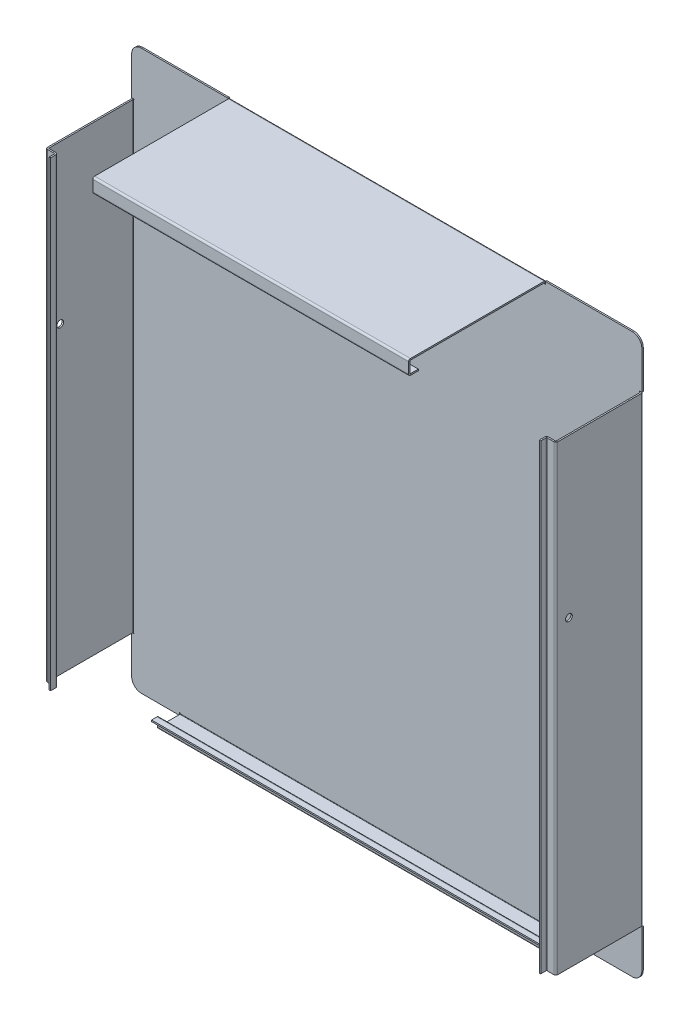
SolidWorks part; units mm, degrees
note: The reader was unsure of these and kept them because the rebuilt part matched: flange length of "边线-法兰1", "边线-法兰4", "边线-法兰5", "边线-法兰2", "边线-法兰3", "边线-法兰6", "边线-法兰7".
ref_plane "前视基准面" through (0, 0, 0) normal (0, 0, 1) x (1, 0, 0)
ref_plane "上视基准面" through (0, 0, 0) normal (0, 1, 0) x (1, 0, 0)
ref_plane "右视基准面" through (0, 0, 0) normal (1, 0, 0) x (0, 0, -1)
sketch "草图2" plane through (0, 0, 0) normal (0, 0, 1) x (1, 0, 0)
  line L1 (-525, 575) -> (525, 575)
  line L2 (-525, 575) -> (-525, -575)
  line L3 (-525, -575) -> (525, -575)
  line L4 (525, 575) -> (525, -575)
  line L5 (-525, 575) -> (525, -575) construction
  line L6 (-525, -575) -> (525, 575) construction
  point P0 (0, 0)
  dimension "D1" = 1050
  dimension "D2" = 1150
base flange "基体-法兰1" sketch "草图2" thickness 3 reverse thickness direction no parameters "D1"=0.7366
edge flange "边线-法兰1" sketch "草图12" flange profiles "草图12", "草图13" flange angle 90 flange length 180 flange position material inside bend radius 0.7366 thickness 3 relief rectangular parameters "D6"=10, "D8"=1
sketch "草图12" plane through (-525, 0, 0) normal (-1, 0, 0) x (0, -1, 0)
  line L0 (-575, 0) -> (575, 0) construction
  line L1 (-475, 0) -> (475, 0)
  line L2 (-475, 0) -> (-475, 177)
  line L3 (-475, 177) -> (475, 177)
  line L4 (475, 177) -> (475, 0)
  dimension "D1" = 100
  dimension "D2" = 100
sketch "草图13" plane through (525, 0, 0) normal (1, 0, 0) x (0, 1, 0)
  line L0 (-575, 0) -> (575, 0) construction
  line L1 (-475, 0) -> (475, 0)
  line L2 (-475, 0) -> (-475, 177)
  line L3 (-475, 177) -> (475, 177)
  line L4 (475, 177) -> (475, 0)
bend "边线折弯2" bend radius 0.7366 bend angle 90 parameters "D5"=2
bend "边线折弯3" bend radius 0.7366 bend angle 90 parameters "D5"=3
edge flange "边线-法兰4" sketch "草图42" flange angle 90 flange length 50 flange position material inside bend radius 0.7366 thickness 3 relief rectangular parameters "D6"=10
sketch "草图42" plane through (0, -575, 0) normal (0, -1, 0) x (1, 0, 0)
  line L0 (-525, 0) -> (525, 0) construction
  line L1 (-425, 0) -> (425, 0)
  line L2 (-425, 0) -> (-425, 47)
  line L3 (-425, 47) -> (425, 47)
  line L4 (425, 47) -> (425, 0)
  line L5 (-525, 0.7366) -> (-525, 177) construction
  line L8 (-525, -3) -> (525, -3) construction
  dimension "D1" = 850
  dimension "D2" = 50
  dimension "D3" = 100
bend "边线折弯13" bend radius 0.7366 bend angle 90 parameters "D5"=5
edge flange "边线-法兰5" sketch "草图49" flange angle 90 flange length 283 flange position material inside bend radius 0.7366 thickness 3 relief rectangular parameters "D6"=10
sketch "草图49" plane through (0, 575, 0) normal (0, 1, 0) x (-1, 0, 0)
  line L0 (-525, 0) -> (525, 0) construction
  line L1 (-325, 0) -> (325, 0)
  line L2 (-325, 0) -> (-325, 280)
  line L3 (-325, 280) -> (325, 280)
  line L4 (325, 280) -> (325, 0)
  line L5 (-525, 0.7366) -> (-525, 177) construction
  line L6 (525, 177) -> (525, 0.7366) construction
  dimension "D1" = 200
  dimension "D2" = 200
bend "边线折弯16" bend radius 0.7366 bend angle 90 parameters "D5"=6
edge flange "边线-法兰2" sketch "草图25" flange profiles "草图25", "草图27", "草图44" flange angle 90 flange length 22 flange position material inside bend radius 0.7366 thickness 3 relief rectangular parameters "D6"=10, "D8"=1
sketch "草图25" plane through (-522, 0, 177) normal (0, 0, 1) x (0, -1, 0)
  line L0 (475, 0) -> (-475, 0) construction
  line L1 (475, 0) -> (-475, 0)
  line L2 (-475, 0) -> (-475, 19)
  line L3 (-475, 19) -> (475, 19)
  line L4 (475, 19) -> (475, 0)
sketch "草图27" plane through (522, 0, 177) normal (0, 0, 1) x (0, 1, 0)
  line L0 (475, 0) -> (-475, 0) construction
  line L1 (475, 0) -> (-475, 0)
  line L2 (-475, 0) -> (-475, 19)
  line L3 (-475, 19) -> (475, 19)
  line L4 (475, 19) -> (475, 0)
sketch "草图44" plane through (0, -572, 47) normal (0, 0, 1) x (1, 0, 0)
  line L0 (425, 0) -> (-425, 0) construction
  line L1 (425, 0) -> (-425, 0)
  line L2 (-425, 0) -> (-425, 19)
  line L3 (-425, 19) -> (425, 19)
  line L4 (425, 19) -> (425, 0)
bend "边线折弯6" bend radius 0.7366 bend angle 90 parameters "D5"=6
bend "边线折弯8" bend radius 0.7366 bend angle 90 parameters "D5"=8
bend "边线折弯14" bend radius 0.7366 bend angle 90 parameters "D5"=12
edge flange "边线-法兰3" sketch "草图36" flange profiles "草图36", "草图39", "草图46" flange angle 90 flange length 15 flange position material inside bend radius 0.7366 thickness 3 relief rectangular parameters "D6"=10, "D8"=1
sketch "草图36" plane through (-503, 0, 177) normal (1, 0, 0) x (0, 1, 0)
  line L0 (-475, 0) -> (475, 0) construction
  line L1 (-475, 0) -> (475, 0)
  line L2 (-475, 0) -> (-475, 12)
  line L3 (-475, 12) -> (475, 12)
  line L4 (475, 12) -> (475, 0)
sketch "草图39" plane through (503, 0, 177) normal (-1, 0, 0) x (0, -1, 0)
  line L0 (-475, 0) -> (475, 0) construction
  line L1 (-475, 0) -> (475, 0)
  line L2 (-475, 0) -> (-475, 12)
  line L3 (-475, 12) -> (475, 12)
  line L4 (475, 12) -> (475, 0)
sketch "草图46" plane through (0, -553, 47) normal (0, 1, 0) x (-1, 0, 0)
  line L0 (-425, 0) -> (425, 0) construction
  line L1 (-425, 0) -> (425, 0)
  line L2 (-425, 0) -> (-425, 12)
  line L3 (-425, 12) -> (425, 12)
  line L4 (425, 12) -> (425, 0)
bend "边线折弯9" bend radius 0.7366 bend angle 90 parameters "D5"=9
bend "边线折弯12" bend radius 0.7366 bend angle 90 parameters "D5"=12
bend "边线折弯15" bend radius 0.7366 bend angle 90 parameters "D5"=16
fillet "圆角1" radius 20 4 edges at (-525, -575, -1.5) (-525, 575, -1.5) (525, 575, -1.5) (525, -575, -1.5)
edge flange "边线-法兰6" sketch "草图56" flange angle 90 flange length 30 flange position material inside bend radius 0.7366 thickness 3 relief rectangular parameters "D6"=10
sketch "草图56" plane through (0, 572, 280) normal (0, 0, 1) x (-1, 0, 0)
  line L0 (325, 0) -> (-325, 0) construction
  line L1 (325, 0) -> (-325, 0)
  line L2 (-325, 0) -> (-325, 27)
  line L3 (-325, 27) -> (325, 27)
  line L4 (325, 27) -> (325, 0)
bend "边线折弯19" bend radius 0.7366 bend angle 90 parameters "D5"=13
edge flange "边线-法兰7" sketch "草图59" flange angle 90 flange length 20 flange position material inside bend radius 0.7366 thickness 3 relief rectangular parameters "D6"=10
sketch "草图59" plane through (0, 545, 277) normal (0, 1, 0) x (1, 0, 0)
  line L1 (325, 0) -> (-325, 0) construction
  line L2 (-325, 0) -> (-325, 17)
  line L3 (-325, 17) -> (325, 17)
  line L4 (325, 17) -> (325, 0)
  line L5 (325, 0) -> (-325, 0)
bend "边线折弯20" bend radius 0.7366 bend angle 90 parameters "D5"=17
sketch "草图60" plane through (-525, 0, 0) normal (-1, 0, 0) x (0, 0, 1)
  line L0 (0, -475) -> (0, 475) construction
  line L1 (0, 0) -> (150, 0) construction
  line L2 (0, 0) -> (0, 150) construction
  line L3 (0, 150) -> (150, 150) construction
  line L4 (150, 0) -> (150, 150) construction
  circle A0 centre (150, 150) radius 7
  dimension "D3" = 14
  dimension "D1" = 150
  dimension "D2" = 150
extrude "切除-拉伸1" cut sketch "草图60" against normal through all normal cut yes
sketch "折弯-线1" plane through (0, 0, 0) normal (0, 1, 0) x (1, 0, 0)
sketch "边界框1" plane through (0, 0, 0) normal (0, 1, 0) x (1, 0, 0)
sheet metal parameters "钣金6" thickness 3 parameters "D1"=0.7366
flat pattern "平板型式6" [suppressed]
sketch "折弯-线2" plane through (0, 0, 0) normal (0, 1, 0) x (1, 0, 0)
sketch "边界框2" [suppressed] plane through (0, 0, 0) normal (0, 1, 0) x (1, 0, 0)
sheet metal parameters "钣金14" thickness 3 parameters "D1"=0.7366
flat pattern "平板型式6" [suppressed]
sketch "折弯-线2" plane through (0, 0, 0) normal (0, 1, 0) x (1, 0, 0)
sketch "边界框2" [suppressed] plane through (0, 0, 0) normal (0, 1, 0) x (1, 0, 0)
bend of the flat pattern "展开-<边线折弯2>1"
bend of the flat pattern "展开-<边线折弯3>1"
sheet metal parameters "钣金16" thickness 3 parameters "D1"=0.7366
flat pattern "平板型式6" [suppressed]
sketch "折弯-线2" plane through (0, 0, 0) normal (0, 1, 0) x (1, 0, 0)
sketch "边界框2" [suppressed] plane through (0, 0, 0) normal (0, 1, 0) x (1, 0, 0)
bend of the flat pattern "展开-<边线折弯2>1"
bend of the flat pattern "展开-<边线折弯3>1"
bend of the flat pattern "展开-<边线折弯13>3"
bend of the flat pattern "展开-<边线折弯16>3"
bend of the flat pattern "展开-<边线折弯6>1"
bend of the flat pattern "展开-<边线折弯8>1"
bend of the flat pattern "展开-<边线折弯14>1"
sheet metal parameters "钣金17" thickness 3 parameters "D1"=0.7366
flat pattern "平板型式6" [suppressed]
sketch "折弯-线2" plane through (0, 0, 0) normal (0, 1, 0) x (1, 0, 0)
sketch "边界框2" [suppressed] plane through (0, 0, 0) normal (0, 1, 0) x (1, 0, 0)
bend of the flat pattern "展开-<边线折弯2>1"
bend of the flat pattern "展开-<边线折弯3>1"
bend of the flat pattern "展开-<边线折弯9>1"
bend of the flat pattern "展开-<边线折弯12>1"
bend of the flat pattern "展开-<边线折弯13>4"
bend of the flat pattern "展开-<边线折弯15>1"
bend of the flat pattern "展开-<边线折弯16>4"
bend of the flat pattern "展开-<边线折弯6>1"
bend of the flat pattern "展开-<边线折弯8>1"
bend of the flat pattern "展开-<边线折弯14>2"
sheet metal parameters "钣金18" thickness 3 parameters "D1"=0.7366
flat pattern "平板型式6" [suppressed]
sketch "折弯-线2" plane through (0, 0, 0) normal (0, 1, 0) x (1, 0, 0)
sketch "边界框2" [suppressed] plane through (0, 0, 0) normal (0, 1, 0) x (1, 0, 0)
bend of the flat pattern "展开-<边线折弯2>1"
bend of the flat pattern "展开-<边线折弯3>1"
bend of the flat pattern "展开-<边线折弯13>1"
sheet metal parameters "钣金19" thickness 3 parameters "D1"=0.7366
flat pattern "平板型式6" [suppressed]
sketch "折弯-线2" plane through (0, 0, 0) normal (0, 1, 0) x (1, 0, 0)
sketch "边界框2" [suppressed] plane through (0, 0, 0) normal (0, 1, 0) x (1, 0, 0)
bend of the flat pattern "展开-<边线折弯2>1"
bend of the flat pattern "展开-<边线折弯3>1"
bend of the flat pattern "展开-<边线折弯13>1"
bend of the flat pattern "展开-<边线折弯16>1"
sheet metal parameters "钣金20" thickness 3 parameters "D1"=0.7366
flat pattern "平板型式6" [suppressed]
sketch "折弯-线2" plane through (0, 0, 0) normal (0, 1, 0) x (1, 0, 0)
sketch "边界框2" [suppressed] plane through (0, 0, 0) normal (0, 1, 0) x (1, 0, 0)
bend of the flat pattern "展开-<边线折弯2>1"
bend of the flat pattern "展开-<边线折弯3>1"
bend of the flat pattern "展开-<边线折弯13>3"
bend of the flat pattern "展开-<边线折弯16>3"
bend of the flat pattern "展开-<边线折弯6>1"
bend of the flat pattern "展开-<边线折弯8>1"
bend of the flat pattern "展开-<边线折弯14>1"
bend of the flat pattern "展开-<边线折弯19>1"
bend of the flat pattern "展开-<边线折弯9>2"
bend of the flat pattern "展开-<边线折弯12>2"
bend of the flat pattern "展开-<边线折弯15>2"
sheet metal parameters "钣金21" thickness 3 parameters "D1"=0.7366
flat pattern "平板型式6" [suppressed]
sketch "折弯-线2" plane through (0, 0, 0) normal (0, 1, 0) x (1, 0, 0)
sketch "边界框2" [suppressed] plane through (0, 0, 0) normal (0, 1, 0) x (1, 0, 0)
bend of the flat pattern "展开-<边线折弯2>1"
bend of the flat pattern "展开-<边线折弯3>1"
bend of the flat pattern "展开-<边线折弯13>3"
bend of the flat pattern "展开-<边线折弯16>3"
bend of the flat pattern "展开-<边线折弯6>1"
bend of the flat pattern "展开-<边线折弯8>1"
bend of the flat pattern "展开-<边线折弯14>1"
bend of the flat pattern "展开-<边线折弯19>1"
bend of the flat pattern "展开-<边线折弯9>2"
bend of the flat pattern "展开-<边线折弯12>2"
bend of the flat pattern "展开-<边线折弯15>2"
bend of the flat pattern "展开-<边线折弯20>1"
sheet metal parameters "钣金22" thickness 3 parameters "D1"=0.7366
flat pattern "平板型式6" [suppressed]
sketch "折弯-线2" plane through (0, 0, 0) normal (0, 1, 0) x (1, 0, 0)
sketch "边界框2" [suppressed] plane through (0, 0, 0) normal (0, 1, 0) x (1, 0, 0)
bend of the flat pattern "展开-<边线折弯2>1"
bend of the flat pattern "展开-<边线折弯3>1"
bend of the flat pattern "展开-<边线折弯13>3"
bend of the flat pattern "展开-<边线折弯16>3"
bend of the flat pattern "展开-<边线折弯6>1"
bend of the flat pattern "展开-<边线折弯8>1"
bend of the flat pattern "展开-<边线折弯14>1"
bend of the flat pattern "展开-<边线折弯19>1"
bend of the flat pattern "展开-<边线折弯9>2"
bend of the flat pattern "展开-<边线折弯12>2"
bend of the flat pattern "展开-<边线折弯15>2"
bend of the flat pattern "展开-<边线折弯20>1"
